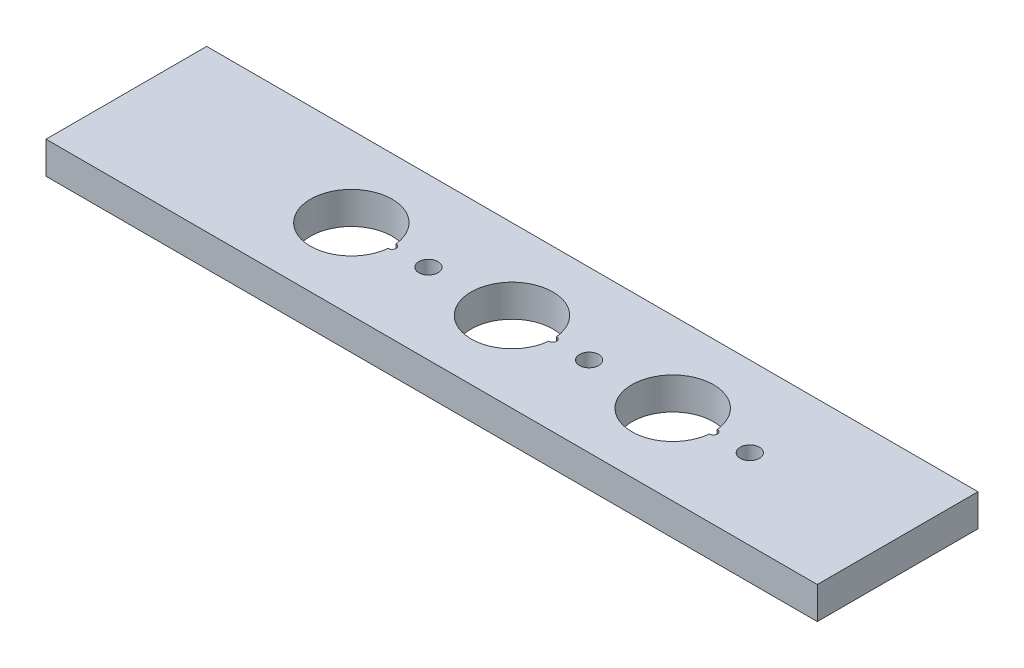
SolidWorks part; units mm, degrees
ref_plane "Front Plane" through (0, 0, 0) normal (0, 0, 1) x (1, 0, 0)
ref_plane "Top Plane" through (0, 0, 0) normal (0, 1, 0) x (1, 0, 0)
ref_plane "Right Plane" through (0, 0, 0) normal (1, 0, 0) x (0, 0, -1)
sketch "Sketch1" plane through (0, 0, 0) normal (0, 1, 0) x (1, 0, 0)
  line L1 (-60, 12.5) -> (60, 12.5)
  line L2 (-60, 12.5) -> (-60, -12.5)
  line L3 (-60, -12.5) -> (60, -12.5)
  line L4 (60, 12.5) -> (60, -12.5)
  circle A0 centre (25, 0) radius 6.35 construction
  arc A1 (31.3217, 0.5993) -> (31.3217, -0.5993) centre (31.35, 0) cw
  arc A2 (31.3217, 0.5993) -> (31.3217, -0.5993) centre (25, 0) ccw
  arc A3 (6.3217, 0.5993) -> (6.3217, -0.5993) centre (6.35, 0) cw
  arc A4 (6.3217, 0.5993) -> (6.3217, -0.5993) centre (0, 0) ccw
  arc A5 (-18.6783, 0.5993) -> (-18.6783, -0.5993) centre (-18.65, 0) cw
  arc A6 (-18.6783, 0.5993) -> (-18.6783, -0.5993) centre (-25, 0) ccw
  circle A7 centre (37, 0) radius 1.5
  circle A8 centre (12, 0) radius 1.5
  circle A9 centre (-13, 0) radius 1.5
  point P4 (0, 12.5)
  point P6 (60, 0)
  dimension "D3" = 12.7
  dimension "D4" = 0.6
  dimension "D7" = 3
  dimension "D1" = 120
  dimension "D2" = 25
  dimension "D6" = 25
  dimension "D8" = 12
  dimension "D5" = 3
  dimension "D9" = 3
extrude "Boss-Extrude1" add sketch "Sketch1" along normal blind 5
